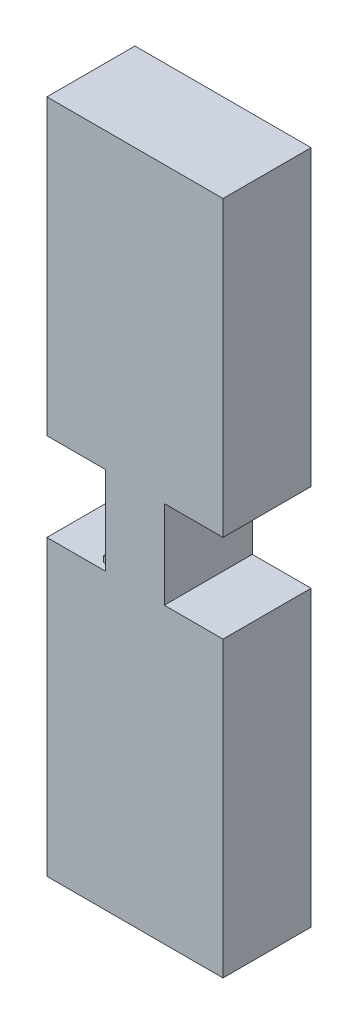
SolidWorks part; units mm, degrees
material "Air"
ref_plane "Front Plane" through (0, 0, 0) normal (0, 0, 1) x (1, 0, 0)
ref_plane "Top Plane" through (0, 0, 0) normal (0, 1, 0) x (1, 0, 0)
ref_plane "Right Plane" through (0, 0, 0) normal (1, 0, 0) x (0, 0, -1)
sketch "Sketch1" plane through (0, 0, 0) normal (0, 0, 1) x (1, 0, 0)
  line L1 (-30, -115) -> (30, -115)
  line L2 (-30, -115) -> (-30, -15)
  line L3 (-30, -15) -> (30, -15)
  line L4 (30, -115) -> (30, -15)
  line L5 (0, -15) -> (0, -115) construction
  line L6 (-30, -65) -> (30, -65) construction
  point P16 (0, -65)
extrude "Boss-Extrude1" add sketch "Sketch1" along normal mid plane 30
sketch "Sketch2" plane through (0, 0, 0) normal (0, 0, 1) x (1, 0, 0)
  line L1 (-30, 15) -> (30, 15)
  line L2 (-30, 15) -> (-30, 115)
  line L3 (-30, 115) -> (30, 115)
  line L4 (30, 15) -> (30, 115)
  line L5 (0, 115) -> (0, 15) construction
  line L6 (-30, 65) -> (30, 65) construction
  point P16 (0, 65)
extrude "Boss-Extrude2" add sketch "Sketch2" along normal mid plane 30
sketch "Sketch3" plane through (0, 0, 0) normal (0, 0, 1) x (1, 0, 0)
  line L0 (30, -15) -> (-30, -15) construction
  line L1 (-10, -15) -> (10, -15)
  line L2 (-10, -15) -> (-10, 15)
  line L3 (-10, 15) -> (10, 15)
  line L4 (10, -15) -> (10, 15)
  line L5 (0, 15) -> (0, -15) construction
  line L6 (-10, 0) -> (10, 0) construction
  line L7 (-30, 15) -> (30, 15) construction
  point P20 (0, 0)
extrude "Boss-Extrude3" add sketch "Sketch3" along normal mid plane 30
sketch "Sketch4" plane through (0, 0, 0) normal (0, 0, 1) x (1, 0, 0)
  line L0 (-10, 15) -> (-10, -15) construction
  line L1 (-11.5, -13.5) -> (-10, -13.5)
  line L2 (-11.5, -13.5) -> (-11.5, -11.5)
  line L3 (-11.5, -11.5) -> (-10, -11.5)
  line L4 (-10, -13.5) -> (-10, -11.5)
  line L5 (-10.75, -11.5) -> (-10.75, -13.5) construction
  line L6 (-11.5, -12.5) -> (-10, -12.5) construction
  point P20 (-10.75, -12.5)
extrude "Boss-Extrude4" add sketch "Sketch4" along normal mid plane 28.5
sketch "Sketch5" plane through (0, 0, 0) normal (0, 0, 1) x (1, 0, 0)
  line L1 (-14.625, -13.5) -> (-11.5, -13.5)
  line L2 (-14.625, -13.5) -> (-14.625, 13.5)
  line L3 (-14.625, 13.5) -> (-11.5, 13.5)
  line L4 (-11.5, -13.5) -> (-11.5, 13.5)
  line L5 (-13.0625, 13.5) -> (-13.0625, -13.5) construction
  line L6 (-14.625, 0) -> (-11.5, 0) construction
  line L7 (-19.25, -13.5) -> (-14.625, -13.5)
  line L8 (-19.25, -13.5) -> (-19.25, 13.5)
  line L9 (-19.25, 13.5) -> (-14.625, 13.5)
  line L10 (-14.625, -13.5) -> (-14.625, 13.5)
  line L11 (-16.9375, 13.5) -> (-16.9375, -13.5) construction
  line L12 (-19.25, 0) -> (-14.625, 0) construction
  line L13 (-23.875, -13.5) -> (-19.25, -13.5)
  line L14 (-23.875, -13.5) -> (-23.875, 13.5)
  line L15 (-23.875, 13.5) -> (-19.25, 13.5)
  line L16 (-19.25, -13.5) -> (-19.25, 13.5)
  line L17 (-21.5625, 13.5) -> (-21.5625, -13.5) construction
  line L18 (-23.875, 0) -> (-19.25, 0) construction
  line L19 (-28.5, -13.5) -> (-23.875, -13.5)
  line L20 (-28.5, -13.5) -> (-28.5, 13.5)
  line L21 (-28.5, 13.5) -> (-23.875, 13.5)
  line L22 (-23.875, -13.5) -> (-23.875, 13.5)
  line L23 (-26.1875, 13.5) -> (-26.1875, -13.5) construction
  line L24 (-28.5, 0) -> (-23.875, 0) construction
  line L25 (11.5, -13.5) -> (14.625, -13.5)
  line L26 (11.5, -13.5) -> (11.5, 13.5)
  line L27 (11.5, 13.5) -> (14.625, 13.5)
  line L28 (14.625, -13.5) -> (14.625, 13.5)
  line L29 (13.0625, 13.5) -> (13.0625, -13.5) construction
  line L30 (11.5, 0) -> (14.625, 0) construction
  line L31 (14.625, -13.5) -> (19.25, -13.5)
  line L32 (14.625, -13.5) -> (14.625, 13.5)
  line L33 (14.625, 13.5) -> (19.25, 13.5)
  line L34 (19.25, -13.5) -> (19.25, 13.5)
  line L35 (16.9375, 13.5) -> (16.9375, -13.5) construction
  line L36 (14.625, 0) -> (19.25, 0) construction
  line L37 (19.25, -13.5) -> (23.875, -13.5)
  line L38 (19.25, -13.5) -> (19.25, 13.5)
  line L39 (19.25, 13.5) -> (23.875, 13.5)
  line L40 (23.875, -13.5) -> (23.875, 13.5)
  line L41 (21.5625, 13.5) -> (21.5625, -13.5) construction
  line L42 (19.25, 0) -> (23.875, 0) construction
  line L43 (23.875, -13.5) -> (28.5, -13.5)
  line L44 (23.875, -13.5) -> (23.875, 13.5)
  line L45 (23.875, 13.5) -> (28.5, 13.5)
  line L46 (28.5, -13.5) -> (28.5, 13.5)
  line L47 (26.1875, 13.5) -> (26.1875, -13.5) construction
  line L48 (23.875, 0) -> (28.5, 0) construction
  point P16 (-13.0625, 0)
  point P24 (-16.9375, 0)
  point P31 (-21.5625, 0)
  point P38 (-26.1875, 0)
  point P46 (13.0625, 0)
  point P53 (16.9375, 0)
  point P60 (21.5625, 0)
  point P67 (26.1875, 0)
